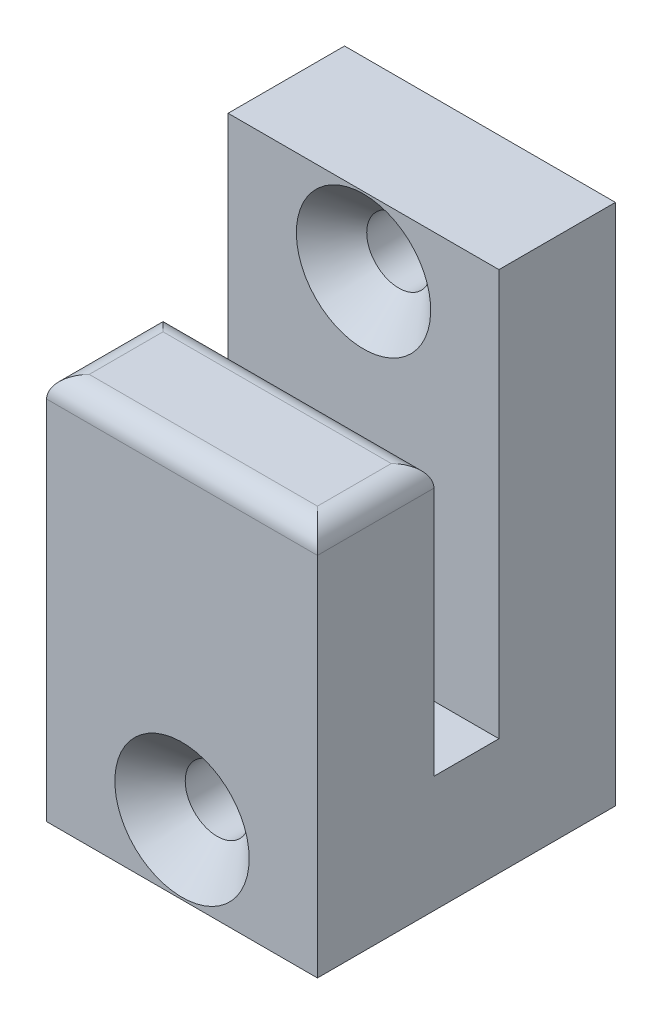
SolidWorks part; units mm, degrees
ref_plane "Front Plane" through (0, 0, 0) normal (0, 0, 1) x (1, 0, 0)
ref_plane "Top Plane" through (0, 0, 0) normal (0, 1, 0) x (1, 0, 0)
ref_plane "Right Plane" through (0, 0, 0) normal (1, 0, 0) x (0, 0, -1)
sketch "Sketch1" plane through (0, 0, 0) normal (1, 0, 0) x (0, 0, -1)
  line L0 (-0.9708, 15.4585) -> (-11.8928, 15.4585)
  line L1 (16.0512, -20.8635) -> (-11.8928, -20.8635)
  line L2 (16.0512, -20.8635) -> (16.0512, 28.1585)
  line L3 (16.0512, 28.1585) -> (5.1292, 28.1585)
  line L4 (-11.8928, -20.8635) -> (-11.8928, 15.4585)
  line L5 (16.0512, -20.8635) -> (-11.8928, 15.4585) construction
  line L6 (16.0512, 28.1585) -> (-11.8928, -20.8635) construction
  line L8 (5.1292, 28.1585) -> (5.1292, -9.9415)
  line L9 (5.1292, -9.9415) -> (-0.9708, -9.9415)
  line L10 (-0.9708, 15.4585) -> (-0.9708, -9.9415)
  line L11 (5.1292, -9.9415) -> (5.1292, -20.8635) construction
  point P0 (0, 0)
  dimension "D1" = 10.922
  dimension "D2" = 6.1
  dimension "D3" = 25.4
  dimension "D4" = 12.7
extrude "Boss-Extrude1" add sketch "Sketch1" along normal blind 25.4
sketch "Sketch2" plane through (0, 0, -16.0512) normal (0, 0, -1) x (-1, 0, 0)
  line L0 (-12.7, 28.1585) -> (-12.7, -20.8635) construction
  line L1 (-25.4, 28.1585) -> (0, 28.1585) construction
  line L2 (-25.4, -20.8635) -> (0, -20.8635) construction
  line L3 (-12.7, 21.6585) -> (-12.7, 28.1585) construction
  line L4 (-12.7, -14.3635) -> (-12.7, -20.8635) construction
  circle A0 centre (-12.7, 21.6585) radius 3
  circle A1 centre (-12.7, -14.3635) radius 3
  dimension "D1" = 6
  dimension "D2" = 6.5
extrude "Cut-Extrude1" cut sketch "Sketch2" against normal through all
chamfer "Chamfer1" distance 3.3 angle 45 2 edges at (9.7, -14.3635, 11.8928) (12.7, 24.6585, -5.1292)
fillet "Fillet1" radius 2 4 edges at (12.7, 15.4585, 0.9708) (25.4, 15.4585, 6.4318) (12.7, 15.4585, 11.8928) (0, 15.4585, 6.4318)
